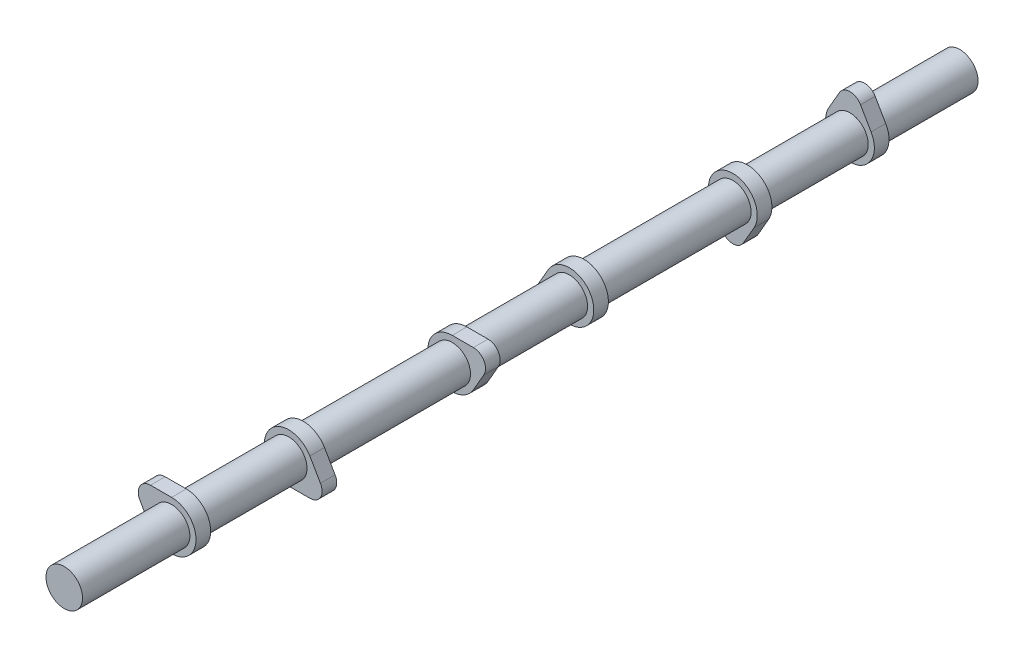
SolidWorks part; units mm, degrees
ref_plane "Front Plane" through (0, 0, 0) normal (0, 0, 1) x (1, 0, 0)
ref_plane "Top Plane" through (0, 0, 0) normal (0, 1, 0) x (1, 0, 0)
ref_plane "Right Plane" through (0, 0, 0) normal (1, 0, 0) x (0, 0, -1)
sketch "Sketch1" plane through (0, 0, 0) normal (0, 0, 1) x (1, 0, 0)
  line L0 (-5.4993, 15.875) -> (-10.9985, 6.35)
  line L1 (5.4993, 15.875) -> (10.9985, 6.35)
  arc A0 (-10.9985, 6.35) -> (10.9985, 6.35) centre (0, 0) ccw
  arc A1 (5.4993, 15.875) -> (-5.4993, 15.875) centre (0, 12.7) ccw
  dimension "D1" = 25.4
  dimension "D2" = 12.7
  dimension "D3" = 12.7
extrude "Boss-Extrude1" add sketch "Sketch1" along normal mid plane 7.62
ref_axis "Axis1" through (0, 0, 181.7306) along (0, 0, -1)
pattern_linear "LPattern1" count 2 spacing 60.96 along (0, 0, 1) of bodies 101
move or copy body "Body-Move/Copy1" bodies to move or copy 102 copy no rotation origin (0, 0, 0) rotation axis (0, 0, 1) rotation angle 180
pattern_linear "LPattern2" count 3 spacing 146.05 along (0, 0, 1) of bodies 101 103
move or copy body "Body-Move/Copy2" bodies to move or copy 104 106 copy no rotation origin (0, 0, 0) rotation axis (0, 0, 1) rotation angle 120
move or copy body "Body-Move/Copy3" bodies to move or copy 107 105 copy no rotation origin (0, 0, 0) rotation axis (0, 0, -1) rotation angle 120
sketch "Sketch2" plane through (0, 0, -3.81) normal (0, 0, -1) x (-1, 0, 0)
  circle A0 centre (0, 0) radius 9.5
  dimension "D1" = 19
extrude "Boss-Extrude2" add sketch "Sketch2" against normal blind 466.09 from offset 49.53
